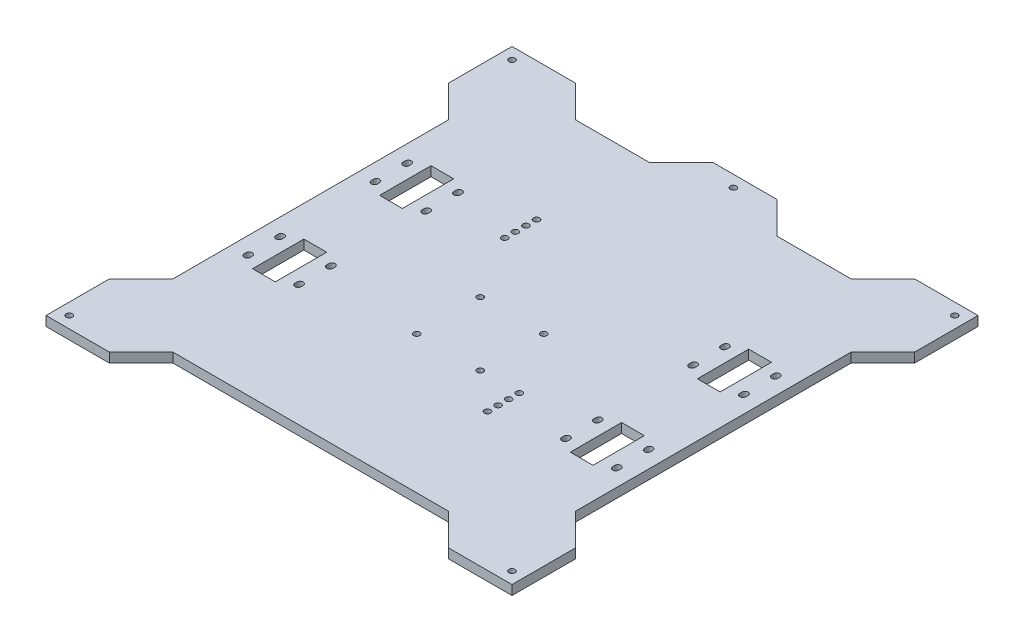
SolidWorks part; units mm, degrees
ref_plane "Front Plane" through (0, 0, 0) normal (0, 0, 1) x (1, 0, 0)
ref_plane "Top Plane" through (0, 0, 0) normal (0, 1, 0) x (1, 0, 0)
ref_plane "Right Plane" through (0, 0, 0) normal (1, 0, 0) x (0, 0, -1)
sketch "Sketch1" plane through (0, 0, 0) normal (0, 1, 0) x (1, 0, 0)
  line L1 (-110, 110) -> (110, 110)
  line L2 (-110, 110) -> (-110, -110)
  line L3 (-110, -110) -> (110, -110)
  line L4 (110, 110) -> (110, -110)
  line L5 (-110, 110) -> (110, -110) construction
  line L6 (-110, -110) -> (110, 110) construction
  point P0 (0, 0)
  dimension "D1" = 220
  dimension "D2" = 220
extrude "Square" add sketch "Sketch1" along normal blind 4.5
sketch "Sketch2" plane through (0, 4.5, 0) normal (0, 1, 0) x (1, 0, 0)
  line L0 (0, 110) -> (0, -110) construction
  line L1 (110, 110) -> (-110, 110) construction
  line L2 (-110, -110) -> (110, -110) construction
  line L3 (-110, 0) -> (110, 0) construction
  line L4 (-110, 110) -> (-110, -110) construction
  line L5 (110, -110) -> (110, 110) construction
  line L6 (75, 110) -> (75, -110) construction
  line L7 (75, 30) -> (0, 30) construction
  line L8 (75, -30) -> (0, -30) construction
  circle A0 centre (87, 38) radius 1.45
  circle A1 centre (87, 22) radius 1.45
  circle A2 centre (63, 22) radius 1.45
  circle A3 centre (63, 38) radius 1.45
  circle A4 centre (-63, 38) radius 1.45
  circle A5 centre (-63, 22) radius 1.45
  circle A6 centre (-87, 22) radius 1.45
  circle A7 centre (-87, 38) radius 1.45
  circle A8 centre (-87, 22) radius 1.45
  circle A9 centre (-87, 38) radius 1.45
  circle A10 centre (-63, 38) radius 1.45
  circle A11 centre (-63, 22) radius 1.45
  circle A12 centre (63, 22) radius 1.45
  circle A13 centre (63, 38) radius 1.45
  circle A14 centre (87, 38) radius 1.45
  circle A15 centre (87, 22) radius 1.45
  circle A16 centre (87, -22) radius 1.45
  circle A17 centre (87, -38) radius 1.45
  circle A18 centre (63, -38) radius 1.45
  circle A19 centre (63, -22) radius 1.45
  circle A20 centre (-63, -22) radius 1.45
  circle A21 centre (-63, -38) radius 1.45
  circle A22 centre (-87, -38) radius 1.45
  circle A23 centre (-87, -22) radius 1.45
  circle A24 centre (-87, -38) radius 1.45
  circle A25 centre (-87, -22) radius 1.45
  circle A26 centre (-63, -22) radius 1.45
  circle A27 centre (-63, -38) radius 1.45
  circle A28 centre (63, -38) radius 1.45
  circle A29 centre (63, -22) radius 1.45
  circle A30 centre (87, -22) radius 1.45
  circle A31 centre (87, -38) radius 1.45
  dimension "D6" = 2.9
  dimension "D7" = 2.9
  dimension "D1" = 75
  dimension "D2" = 30
  dimension "D3" = 16
  dimension "D5" = 12
extrude "LM8UU-Holders" cut sketch "Sketch2" against normal through all contours A7 | A6 | A5 | A4 | A20 | A21 | A22 | A23 | A19 | A18 | A17 | A16 | A1 | A0 | A3 | A2 region at (87, 4.5, -38) region at (87, 4.5, -22) region at (63, 4.5, -22) region at (63, 4.5, -38) region at (-63, 4.5, -38) region at (-63, 4.5, -22) region at (-87, 4.5, -22) region at (-87, 4.5, -38) region at (87, 4.5, 22) region at (87, 4.5, 38) region at (63, 4.5, 38) region at (63, 4.5, 22) region at (-63, 4.5, 22) region at (-63, 4.5, 38) region at (-87, 4.5, 38) region at (-87, 4.5, 22)
sketch "Sketch10" plane through (0, 4.5, 0) normal (0, 1, 0) x (1, 0, 0)
  line L0 (0, 110) -> (0, -79.9796) construction
  line L3 (-26.5242, 0) -> (110, 0) construction
  line L6 (75, 110) -> (75, -110) construction
  line L7 (75, 30) -> (-75, 30) construction
  line L8 (87, 22) -> (87, 23) construction
  line L9 (110, 110) -> (-110, 110) construction
  line L10 (110, -110) -> (110, 110) construction
  line L11 (85.55, 22) -> (85.55, 23)
  line L12 (88.45, 22) -> (88.45, 23)
  line L13 (87, 38) -> (87, 37) construction
  line L14 (88.45, 38) -> (88.45, 37)
  line L15 (85.55, 38) -> (85.55, 37)
  line L16 (63, 38) -> (63, 37) construction
  line L17 (61.55, 38) -> (61.55, 37)
  line L18 (64.45, 38) -> (64.45, 37)
  line L19 (63, 22) -> (63, 23) construction
  line L20 (64.45, 22) -> (64.45, 23)
  line L21 (61.55, 22) -> (61.55, 23)
  line L22 (75, -30) -> (-75, -30) construction
  line L23 (87, -22) -> (87, -23) construction
  line L24 (85.55, -22) -> (85.55, -23)
  line L25 (88.45, -22) -> (88.45, -23)
  line L26 (87, -38) -> (87, -37) construction
  line L27 (88.45, -38) -> (88.45, -37)
  line L28 (85.55, -38) -> (85.55, -37)
  line L29 (63, -38) -> (63, -37) construction
  line L30 (61.55, -38) -> (61.55, -37)
  line L31 (64.45, -38) -> (64.45, -37)
  line L32 (63, -22) -> (63, -23) construction
  line L33 (64.45, -22) -> (64.45, -23)
  line L34 (61.55, -22) -> (61.55, -23)
  line L35 (26.5242, 0) -> (-110, 0) construction
  line L36 (-87, 22) -> (-87, 23) construction
  line L37 (-85.55, 22) -> (-85.55, 23)
  line L38 (-88.45, 22) -> (-88.45, 23)
  line L39 (-87, 38) -> (-87, 37) construction
  line L40 (-88.45, 38) -> (-88.45, 37)
  line L41 (-85.55, 38) -> (-85.55, 37)
  line L42 (-63, 38) -> (-63, 37) construction
  line L43 (-61.55, 38) -> (-61.55, 37)
  line L44 (-64.45, 38) -> (-64.45, 37)
  line L45 (-63, 22) -> (-63, 23) construction
  line L46 (-64.45, 22) -> (-64.45, 23)
  line L47 (-61.55, 22) -> (-61.55, 23)
  line L48 (-87, -22) -> (-87, -23) construction
  line L49 (-85.55, -22) -> (-85.55, -23)
  line L50 (-88.45, -22) -> (-88.45, -23)
  line L51 (-87, -38) -> (-87, -37) construction
  line L52 (-88.45, -38) -> (-88.45, -37)
  line L53 (-85.55, -38) -> (-85.55, -37)
  line L54 (-63, -38) -> (-63, -37) construction
  line L55 (-61.55, -38) -> (-61.55, -37)
  line L56 (-64.45, -38) -> (-64.45, -37)
  line L57 (-63, -22) -> (-63, -23) construction
  line L58 (-64.45, -22) -> (-64.45, -23)
  line L59 (-61.55, -22) -> (-61.55, -23)
  arc A0 (61.55, 38) -> (64.45, 38) centre (63, 38) cw
  arc A1 (88.45, 38) -> (85.55, 38) centre (87, 38) ccw
  arc A2 (85.55, 22) -> (88.45, 22) centre (87, 22) ccw
  arc A3 (88.45, 23) -> (85.55, 23) centre (87, 23) ccw
  arc A4 (85.55, 37) -> (88.45, 37) centre (87, 37) ccw
  arc A5 (64.45, 37) -> (61.55, 37) centre (63, 37) cw
  arc A6 (64.45, 22) -> (61.55, 22) centre (63, 22) cw
  arc A7 (61.55, 23) -> (64.45, 23) centre (63, 23) cw
  arc A8 (85.55, -22) -> (88.45, -22) centre (87, -22) cw
  arc A9 (88.45, -23) -> (85.55, -23) centre (87, -23) cw
  arc A10 (88.45, -38) -> (85.55, -38) centre (87, -38) cw
  arc A11 (85.55, -37) -> (88.45, -37) centre (87, -37) cw
  arc A12 (61.55, -38) -> (64.45, -38) centre (63, -38) ccw
  arc A13 (64.45, -37) -> (61.55, -37) centre (63, -37) ccw
  arc A14 (64.45, -22) -> (61.55, -22) centre (63, -22) ccw
  arc A15 (61.55, -23) -> (64.45, -23) centre (63, -23) ccw
  arc A16 (-85.55, 22) -> (-88.45, 22) centre (-87, 22) cw
  arc A17 (-88.45, 23) -> (-85.55, 23) centre (-87, 23) cw
  arc A18 (-88.45, 38) -> (-85.55, 38) centre (-87, 38) cw
  arc A19 (-85.55, 37) -> (-88.45, 37) centre (-87, 37) cw
  arc A20 (-61.55, 38) -> (-64.45, 38) centre (-63, 38) ccw
  arc A21 (-64.45, 37) -> (-61.55, 37) centre (-63, 37) ccw
  arc A22 (-64.45, 22) -> (-61.55, 22) centre (-63, 22) ccw
  arc A23 (-61.55, 23) -> (-64.45, 23) centre (-63, 23) ccw
  arc A24 (-85.55, -22) -> (-88.45, -22) centre (-87, -22) ccw
  arc A25 (-88.45, -23) -> (-85.55, -23) centre (-87, -23) ccw
  arc A26 (-88.45, -38) -> (-85.55, -38) centre (-87, -38) ccw
  arc A27 (-85.55, -37) -> (-88.45, -37) centre (-87, -37) ccw
  arc A28 (-61.55, -38) -> (-64.45, -38) centre (-63, -38) cw
  arc A29 (-64.45, -37) -> (-61.55, -37) centre (-63, -37) cw
  arc A30 (-64.45, -22) -> (-61.55, -22) centre (-63, -22) cw
  arc A31 (-61.55, -23) -> (-64.45, -23) centre (-63, -23) cw
  point P8 (87, 22.5)
  point P19 (87, 37.5)
  point P28 (63, 37.5)
  point P35 (63, 22.5)
  point P44 (87, -22.5)
  point P51 (87, -37.5)
  point P58 (63, -37.5)
  point P65 (63, -22.5)
  point P73 (0, 30)
  point P74 (0, -30)
  point P76 (-87, 22.5)
  point P83 (-87, 37.5)
  point P90 (-63, 37.5)
  point P97 (-63, 22.5)
  point P104 (-87, -22.5)
  point P111 (-87, -37.5)
  point P118 (-63, -37.5)
  point P125 (-63, -22.5)
  dimension "D1" = 75
  dimension "D2" = 30
  dimension "D3" = 16
  dimension "D5" = 12
  dimension "D4" = 1.45
  dimension "D7" = 1.45
  dimension "D8" = 1
  dimension "D9" = 1
sketch "Sketch3" plane through (0, 4.5, 0) normal (0, 1, 0) x (1, 0, 0)
  line L0 (0, -110) -> (0, 110) construction
  line L1 (-110, -110) -> (110, -110) construction
  line L2 (110, 110) -> (-110, 110) construction
  line L3 (110, -15) -> (-110, -15) construction
  line L6 (15, -30) -> (-15, -30) construction
  line L7 (15, 0) -> (-15, 0) construction
  line L8 (110, -110) -> (110, 110) construction
  line L9 (-110, 110) -> (-110, -110) construction
  line L10 (110, 0) -> (-110, 0) construction
  circle A0 centre (-15, -30) radius 1.45
  circle A1 centre (15, -30) radius 1.45
  circle A2 centre (15, 0) radius 1.45
  circle A3 centre (-15, 0) radius 1.45
  point P16 (0, -30)
  dimension "D1" = 2.9
  dimension "D2" = 15
  dimension "D3" = 15
  dimension "D5" = 15
extrude "DefaultBelt" cut sketch "Sketch3" against normal through all
sketch "Sketch4" plane through (0, 4.5, 0) normal (0, 1, 0) x (1, 0, 0)
  line L0 (0, 110) -> (0, -110) construction
  line L1 (110, 110) -> (-110, 110) construction
  line L2 (-110, -110) -> (110, -110) construction
  line L3 (-15, -1.45) -> (-15, -28.55) construction
  line L4 (15, -28.55) -> (15, -1.45) construction
  line L5 (15, -15) -> (-15, -15) construction
  arc A0 (-0.7348, 6.25) -> (0.7348, 6.25) centre (0, 5) ccw
  arc A1 (0.7348, 6.25) -> (-0.7348, 6.25) centre (0, 7.5) ccw
  arc A2 (0.7348, -36.25) -> (-0.7348, -36.25) centre (0, -37.5) cw
  arc A3 (-0.7348, -36.25) -> (0.7348, -36.25) centre (0, -35) cw
  circle A4 centre (-15, 0) radius 1.45 construction
  circle A5 centre (-15, -30) radius 1.45 construction
  circle A6 centre (15, -30) radius 1.45 construction
  circle A7 centre (15, 0) radius 1.45 construction
  dimension "D1" = 2.9
  dimension "D2" = 2.9
  dimension "D3" = 20
  dimension "D4" = 22.5
extrude "BeltOptions" [suppressed] cut sketch "Sketch4" against normal through all
sketch "Sketch5" plane through (0, 4.5, 0) normal (0, 1, 0) x (1, 0, 0)
  line L0 (-110, 0) -> (110, 0) construction
  line L1 (-110, 110) -> (-110, -110) construction
  line L2 (110, -110) -> (110, 110) construction
  line L3 (0, 110) -> (0, -110) construction
  line L4 (110, 110) -> (-110, 110) construction
  line L5 (-110, 110) -> (-110, 80)
  line L6 (-110, 80) -> (-95, 65)
  line L7 (-95, 65) -> (-95, -65)
  line L8 (0, 0) -> (-110, 110) construction
  line L9 (-65, 95) -> (65, 95)
  line L10 (-80, 110) -> (-65, 95)
  line L11 (-110, 110) -> (-80, 110)
  line L12 (-95, 65) -> (-95, -65)
  line L13 (0, 0) -> (110, 110) construction
  line L14 (95, 65) -> (95, -65)
  line L15 (110, 110) -> (80, 110)
  line L16 (80, 110) -> (65, 95)
  line L17 (95, 65) -> (95, -65)
  line L18 (110, 80) -> (95, 65)
  line L19 (110, 110) -> (110, 80)
  line L20 (0, 0) -> (110, -110) construction
  line L21 (0, 0) -> (-110, -110) construction
  line L22 (110, -110) -> (110, -80)
  line L23 (110, -80) -> (95, -65)
  line L24 (80, -110) -> (65, -95)
  line L25 (110, -110) -> (80, -110)
  line L26 (-110, -110) -> (-80, -110)
  line L27 (-80, -110) -> (-65, -95)
  line L28 (-65, -95) -> (65, -95)
  line L29 (-110, -80) -> (-95, -65)
  line L30 (-110, -110) -> (-110, -80)
  point P24 (0, 95)
  point P32 (95, 0)
  point P35 (-95, 0)
  point P36 (0, -95)
  circle M16 centre (15, -30) radius 1.45
  circle M18 centre (63, 38) radius 1.45
  circle M20 centre (87, 22) radius 1.45
  circle M22 centre (87, -38) radius 1.45
  circle M23 centre (63, -38) radius 1.45
  circle M24 centre (63, -22) radius 1.45
  circle M25 centre (-87, -22) radius 1.45
  circle M26 centre (-87, -38) radius 1.45
  circle M27 centre (-63, -38) radius 1.45
  circle M28 centre (-63, -22) radius 1.45
  circle M29 centre (-63, 38) radius 1.45
  circle M30 centre (-63, 22) radius 1.45
  circle M31 centre (-87, 22) radius 1.45
  circle M32 centre (-87, 38) radius 1.45
  line M33 (110, -110) -> (110, 110)
  line M34 (110, 110) -> (-110, 110)
  line M35 (-110, 110) -> (-110, -110)
  line M36 (-110, -110) -> (110, -110)
  dimension "D1" = 15
  dimension "D2" = 30
  dimension "D3" = 45
  dimension "D4" = 45
extrude "Shaping" cut sketch "Sketch5" against normal blind 10 flip side to cut contours L29 L27 L28 L24 L23 L14 L18 L16 L9 L10 L6 L7 M35 M36 M33 M34 M16 M18 M20 M22 M24 M26 M28 M30 M32 M31 M29 M27 M25 M23 region at (0.037, 4.5, -0.0113)
sketch "Sketch6" plane through (0, 4.5, 0) normal (0, 1, 0) x (1, 0, 0)
  line L0 (-110, 110) -> (110, -110) construction
  line L1 (-110, -110) -> (110, 110) construction
  line L2 (110, 80) -> (110, 110) construction
  line L3 (0, 95) -> (0, -95) construction
  line L4 (-65, 95) -> (65, 95) construction
  line L5 (-65, -95) -> (65, -95) construction
  line L6 (-95, 0) -> (95, 0) construction
  line L7 (-95, 65) -> (-95, -65) construction
  line L8 (95, 65) -> (95, -65) construction
  circle A0 centre (-104.5, 104.5) radius 1.45
  circle A1 centre (104.5, 104.5) radius 1.45
  circle A2 centre (104.5, -104.5) radius 1.45
  circle A3 centre (-104.5, -104.5) radius 1.45
  dimension "D2" = 2.9
  dimension "D1" = 45
  dimension "D3" = 104.5
extrude "Cut-Extrude5" cut sketch "Sketch6" against normal through all
sketch "Sketch7" plane through (0, 4.5, 0) normal (0, 1, 0) x (1, 0, 0)
  line L0 (-87, 38) -> (-63, 22) construction
  line L1 (-63, 22) -> (-87, 22) construction
  line L2 (-87, 22) -> (-63, 38) construction
  line L3 (-63, 38) -> (-87, 38) construction
  line L4 (-95, 0) -> (95, 0) construction
  line L5 (-80.375, 42.125) -> (-69.625, 42.125)
  line L6 (-80.375, 42.125) -> (-80.375, 17.875)
  line L7 (-80.375, 17.875) -> (-69.625, 17.875)
  line L8 (-69.625, 42.125) -> (-69.625, 17.875)
  line L9 (-80.375, 42.125) -> (-69.625, 17.875) construction
  line L10 (-80.375, 17.875) -> (-69.625, 42.125) construction
  line L11 (-95, 65) -> (-95, -65) construction
  line L12 (95, 65) -> (95, -65) construction
  line L13 (0, -95) -> (0, 95) construction
  line L14 (-65, -95) -> (65, -95) construction
  line L15 (-65, 95) -> (65, 95) construction
  line L16 (-80.375, -17.875) -> (-69.625, -42.125) construction
  line L17 (-80.375, -42.125) -> (-69.625, -17.875) construction
  line L18 (-63, -38) -> (-87, -38) construction
  line L19 (-87, -22) -> (-63, -38) construction
  line L20 (-63, -22) -> (-87, -22) construction
  line L21 (-87, -38) -> (-63, -22) construction
  line L22 (-69.625, -42.125) -> (-69.625, -17.875)
  line L23 (-80.375, -17.875) -> (-69.625, -17.875)
  line L24 (-80.375, -42.125) -> (-80.375, -17.875)
  line L25 (-80.375, -42.125) -> (-69.625, -42.125)
  line L26 (-80.375, 17.875) -> (-69.625, 42.125) construction
  line L27 (80.375, 17.875) -> (69.625, 42.125) construction
  line L28 (87, -38) -> (63, -22) construction
  line L29 (63, -22) -> (87, -22) construction
  line L30 (87, -22) -> (63, -38) construction
  line L31 (63, -38) -> (87, -38) construction
  line L32 (80.375, -42.125) -> (69.625, -17.875) construction
  line L33 (80.375, -17.875) -> (69.625, -42.125) construction
  line L34 (80.375, 17.875) -> (69.625, 42.125) construction
  line L35 (80.375, 42.125) -> (69.625, 17.875) construction
  line L36 (63, 38) -> (87, 38) construction
  line L37 (87, 22) -> (63, 38) construction
  line L38 (63, 22) -> (87, 22) construction
  line L39 (87, 38) -> (63, 22) construction
  line L40 (80.375, -42.125) -> (69.625, -42.125)
  line L41 (80.375, -42.125) -> (80.375, -17.875)
  line L42 (80.375, -17.875) -> (69.625, -17.875)
  line L43 (69.625, -42.125) -> (69.625, -17.875)
  line L44 (69.625, 42.125) -> (69.625, 17.875)
  line L45 (80.375, 17.875) -> (69.625, 17.875)
  line L46 (80.375, 42.125) -> (80.375, 17.875)
  line L47 (80.375, 42.125) -> (69.625, 42.125)
  point P4 (-75, 30)
  point P33 (-75, -30)
  point P50 (75, -30)
  point P51 (75, 30)
  dimension "D1" = 10.75
  dimension "D2" = 24.25
extrude "Cut-Extrude6" cut sketch "Sketch7" against normal through all
sketch "Sketch8" plane through (0, 4.5, 0) normal (0, 1, 0) x (1, 0, 0)
  line L0 (0, 0) -> (0, 95) construction
  line L1 (0, 0) -> (-66.8115, 0) construction
  line L3 (-65, 95) -> (65, 95) construction
  line L4 (-33.45, 45) -> (-33.45, 30) construction
  line L5 (-33.45, 45) -> (-33.45, 30) construction
  line L6 (33.45, -45) -> (33.45, -30) construction
  circle A0 centre (-33.45, 45) radius 1.45
  circle A1 centre (-33.45, 40) radius 1.45
  circle A2 centre (-33.45, 35) radius 1.45
  circle A3 centre (-33.45, 30) radius 1.45
  circle A8 centre (33.45, -45) radius 1.45
  circle A9 centre (33.45, -40) radius 1.45
  circle A10 centre (33.45, -35) radius 1.45
  circle A11 centre (33.45, -30) radius 1.45
  dimension "D1" = 2.9
  dimension "D2" = 50
  dimension "D4" = 33.45
extrude "EndstopTrigger" cut sketch "Sketch8" against normal through all
pattern_linear "LPattern1" [suppressed] count 2 spacing 30 of bodies 108
sketch "Sketch9" plane through (0, 4.5, 0) normal (0, 1, 0) x (1, 0, 0)
  line L0 (-80, 110) -> (-110, 110) construction
  line L1 (-65, 95) -> (65, 95) construction
  line L7 (-95, 0) -> (95, 0) construction
  line L8 (-95, 65) -> (-95, -65) construction
  line L11 (95, 65) -> (95, -65) construction
  line L12 (-104.5, 104.5) -> (104.5, 104.5) construction
  line L13 (0, 110) -> (0, 95) construction
  line L14 (-80, 110) -> (80, 110) construction
  line L15 (15, 110) -> (30, 95)
  line L16 (-30, 95) -> (30, 95)
  line L17 (-15, 110) -> (-30, 95)
  line L18 (15, 110) -> (-15, 110)
  circle A1 centre (0, 104.5) radius 1.45
  dimension "D2" = 30
  dimension "D3" = 2.9
  dimension "D1" = 45
  dimension "D4" = 45
extrude "Boss-Extrude1" add sketch "Sketch9" against normal through all
extrude "HolesToSlots" cut sketch "Sketch10" against normal through all
sketch "Sketch11" plane through (0, 4.5, 0) normal (0, 1, 0) x (1, 0, 0)
  line L0 (0, -95) -> (0, 0) construction
  line L1 (-65, -95) -> (65, -95) construction
  line L2 (95, 0) -> (0, 0) construction
  line L3 (95, 65) -> (95, -65) construction
  line L4 (0, 0) -> (110, -110) construction
  line L5 (-69.1421, -85) -> (-5, -85)
  line L6 (-69.1421, -85) -> (-84.1421, -100)
  line L7 (-84.1421, -100) -> (-100, -100)
  line L8 (-100, -100) -> (-100, -84.1421)
  line L9 (-100, -84.1421) -> (-85, -69.1421)
  line L10 (-85, -69.1421) -> (-85, -52.125)
  line L11 (-85, -52.125) -> (-5, -52.125)
  line L12 (-80, -110) -> (-65, -95) construction
  line L13 (-110, -80) -> (-95, -65) construction
  line L14 (-110, -80) -> (-110, -110) construction
  line L15 (-110, -110) -> (-80, -110) construction
  line L16 (-80.375, -42.125) -> (-69.625, -42.125) construction
  line L17 (-95, 65) -> (-95, -65) construction
  line L18 (-5, -52.125) -> (-5, -85)
  line L19 (5, -52.125) -> (5, -85)
  line L20 (85, -52.125) -> (5, -52.125)
  line L21 (85, -69.1421) -> (85, -52.125)
  line L22 (100, -84.1421) -> (85, -69.1421)
  line L23 (100, -100) -> (100, -84.1421)
  line L24 (84.1421, -100) -> (100, -100)
  line L25 (69.1421, -85) -> (84.1421, -100)
  line L26 (69.1421, -85) -> (5, -85)
  line L27 (69.1421, 85) -> (5, 85)
  line L28 (69.1421, 85) -> (84.1421, 100)
  line L29 (84.1421, 100) -> (100, 100)
  line L30 (100, 100) -> (100, 84.1421)
  line L31 (100, 84.1421) -> (85, 69.1421)
  line L32 (85, 69.1421) -> (85, 52.125)
  line L33 (85, 52.125) -> (5, 52.125)
  line L34 (5, 52.125) -> (5, 85)
  line L35 (-5, 52.125) -> (-5, 85)
  line L36 (-85, 52.125) -> (-5, 52.125)
  line L37 (-85, 69.1421) -> (-85, 52.125)
  line L38 (-100, 84.1421) -> (-85, 69.1421)
  line L39 (-100, 100) -> (-100, 84.1421)
  line L40 (-84.1421, 100) -> (-100, 100)
  line L41 (-69.1421, 85) -> (-84.1421, 100)
  line L42 (-69.1421, 85) -> (-5, 85)
  dimension "D1" = 10
  dimension "D2" = 10
  dimension "D3" = 10
  dimension "D4" = 10
  dimension "D5" = 10
  dimension "D6" = 10
  dimension "D7" = 10
  dimension "D8" = 5
extrude "Cut-Extrude7" [suppressed] cut sketch "Sketch11" against normal through all
sketch "Sketch12" [suppressed] plane through (0, 4.5, 0) normal (0, 1, 0) x (1, 0, 0)
  line L0 (0, 0) -> (-110, -110) construction
  line L1 (-110, -110) -> (-80, -110) construction
  line L2 (-110, -80) -> (80, 110) construction
  line L3 (110, 80) -> (-80, -110) construction
  line L4 (-95, -65) -> (-65, -95) construction
  line L5 (0, 0) -> (0, -95) construction
  line L6 (-65, -95) -> (65, -95) construction
  line L7 (95, 0) -> (-95, 0) construction
  line L8 (-95, 65) -> (-95, -65) construction
  line L9 (-100, -100) -> (-100, -84.1421)
  line L10 (-100, -84.1421) -> (-59.2893, -43.4315)
  line L11 (-59.2893, -43.4315) -> (-43.4315, -43.4315)
  line L12 (-110, -80) -> (-110, -110) construction
  line L13 (-100, -100) -> (-84.1421, -100)
  line L14 (-84.1421, -100) -> (-43.4315, -59.2893)
  line L15 (-43.4315, -59.2893) -> (-43.4315, -43.4315)
  line L16 (55, -85) -> (-55, -85)
  line L17 (-55, -85) -> (-29.2893, -59.2893)
  line L18 (-29.2893, -59.2893) -> (29.2893, -59.2893)
  line L19 (95, -65) -> (65, -95) construction
  line L20 (0, 0) -> (110, -110) construction
  line L21 (55, -85) -> (29.2893, -59.2893)
  line L22 (43.4315, -59.2893) -> (43.4315, -43.4315)
  line L23 (84.1421, -100) -> (43.4315, -59.2893)
  line L24 (100, -100) -> (84.1421, -100)
  line L25 (59.2893, -43.4315) -> (43.4315, -43.4315)
  line L26 (100, -84.1421) -> (59.2893, -43.4315)
  line L27 (100, -100) -> (100, -84.1421)
  line L28 (95, 65) -> (65, 95) construction
  line L29 (-95, 65) -> (-65, 95) construction
  line L30 (100, 100) -> (100, 84.1421)
  line L31 (100, 84.1421) -> (59.2893, 43.4315)
  line L32 (59.2893, 43.4315) -> (43.4315, 43.4315)
  line L33 (100, 100) -> (84.1421, 100)
  line L34 (84.1421, 100) -> (43.4315, 59.2893)
  line L35 (43.4315, 59.2893) -> (43.4315, 43.4315)
  line L36 (55, 85) -> (29.2893, 59.2893)
  line L37 (-29.2893, 59.2893) -> (29.2893, 59.2893)
  line L38 (-55, 85) -> (-29.2893, 59.2893)
  line L39 (55, 85) -> (-55, 85)
  line L40 (-43.4315, 59.2893) -> (-43.4315, 43.4315)
  line L41 (-84.1421, 100) -> (-43.4315, 59.2893)
  line L42 (-100, 100) -> (-84.1421, 100)
  line L43 (-59.2893, 43.4315) -> (-43.4315, 43.4315)
  line L44 (-100, 84.1421) -> (-59.2893, 43.4315)
  line L45 (-100, 100) -> (-100, 84.1421)
  point P40 (0, -59.2893)
  point P41 (0, -85)
  point P67 (0, 85)
  point P68 (0, 59.2893)
  dimension "D1" = 10
  dimension "D2" = 10
  dimension "D3" = 80
  dimension "D4" = 10
  dimension "D5" = 10
  dimension "D6" = 0
extrude "Cut-Extrude8" [suppressed] cut sketch "Sketch12" against normal through all
sketch "Sketch14" [suppressed] plane through (0, 4.5, 0) normal (0, 1, 0) x (1, 0, 0)
  line L0 (0, 85) -> (0, 110) construction
  line L1 (55, 85) -> (-55, 85) construction
  line L2 (15, 110) -> (-15, 110) construction
  line L3 (10.8579, 100) -> (-10.8579, 100)
  line L4 (-10.8579, 100) -> (-25.8579, 85)
  line L5 (-25.8579, 85) -> (25.8579, 85)
  line L6 (-15, 110) -> (-30, 95) construction
  line L7 (10.8579, 100) -> (25.8579, 85)
  point P13 (0, 100)
  dimension "D1" = 10
  dimension "D2" = 10
extrude "Cut-Extrude10" [suppressed] cut sketch "Sketch14" against normal through all
sketch "Sketch13" [suppressed] plane through (0, 4.5, 0) normal (0, 1, 0) x (1, 0, 0)
  line L0 (-59.2893, 43.4315) -> (-59.2893, -43.4315) construction
  line L1 (-100, 84.1421) -> (-59.2893, 43.4315) construction
  line L2 (-59.2893, 0) -> (0, 0) construction
  line L3 (-59.2893, 33.4315) -> (-59.2893, -33.4315)
  line L4 (-59.2893, -33.4315) -> (-43.4315, -33.4315)
  line L5 (-43.4315, -33.4315) -> (-43.4315, 33.4315)
  line L6 (-43.4315, 33.4315) -> (-59.2893, 33.4315)
  line L7 (-59.2893, 43.4315) -> (-43.4315, 43.4315) construction
  line L8 (-43.4315, -43.4315) -> (-59.2893, -43.4315) construction
  line L9 (-43.4315, 43.4315) -> (-43.4315, 59.2893) construction
  line L10 (0, 0) -> (0, 43.4315) construction
  line L11 (59.2893, 43.4315) -> (59.2893, -43.4315) construction
  line L12 (43.4315, 33.4315) -> (59.2893, 33.4315)
  line L13 (43.4315, -33.4315) -> (43.4315, 33.4315)
  line L14 (59.2893, -33.4315) -> (43.4315, -33.4315)
  line L15 (59.2893, 33.4315) -> (59.2893, -33.4315)
  line L16 (110, -110) -> (0, 0) construction
  line L17 (55, -85) -> (29.2893, -59.2893) construction
  line L18 (-33.4315, -43.2893) -> (33.4315, -43.2893)
  line L19 (-33.4315, -43.2893) -> (-33.4315, -63.4315)
  line L20 (-33.4315, -63.4315) -> (33.4315, -63.4315)
  line L21 (33.4315, -43.2893) -> (33.4315, -63.4315)
  line L22 (-33.4315, -43.2893) -> (33.4315, -63.4315) construction
  line L23 (-33.4315, -63.4315) -> (33.4315, -43.2893) construction
  line L24 (-43.4315, -59.2893) -> (-43.4315, -43.4315) construction
  line L25 (0, -53.3604) -> (0, -63.4315) construction
  line L26 (55, 85) -> (25.8579, 85) construction
  line L28 (43.4315, -43.4315) -> (43.4315, -59.2893) construction
  line L29 (29.2893, -59.2893) -> (-29.2893, -59.2893) construction
  line L30 (43.4315, 59.2893) -> (43.4315, 43.4315) construction
  line L31 (-33.4315, 83) -> (33.4315, 83)
  line L32 (-33.4315, 83) -> (-33.4315, 15)
  line L33 (-33.4315, 15) -> (33.4315, 15)
  line L34 (33.4315, 83) -> (33.4315, 15)
  line L35 (-33.4315, 83) -> (33.4315, 15) construction
  line L36 (-33.4315, 15) -> (33.4315, 83) construction
  point P27 (0, -53.3604)
  point P43 (0, 49)
  dimension "D1" = 10
  dimension "D2" = 10
  dimension "D3" = 10
  dimension "D4" = 10
  dimension "D5" = 16
  dimension "D6" = 10
  dimension "D7" = 10
  dimension "D8" = 15
  dimension "D9" = 2
extrude "Cut-Extrude9" [suppressed] cut sketch "Sketch13" against normal through all
sketch "Sketch15" [suppressed] plane through (0, 4.5, 0) normal (0, 1, 0) x (1, 0, 0)
  line L0 (-59.2893, 0) -> (-95, 0) construction
  line L1 (-59.2893, 33.4315) -> (-59.2893, -33.4315) construction
  line L2 (-95, 65) -> (-95, -65) construction
  line L3 (-80.5, 17.875) -> (-69.5, 17.875) construction
  line L4 (-59.2893, -15) -> (-59.2893, -7.875)
  line L5 (-85, -7.875) -> (-85, 7.875)
  line L6 (-85, 7.875) -> (-66.4143, 7.875)
  line L7 (-59.2893, -7.875) -> (-59.2893, 7.875)
  line L8 (-66.4143, -7.875) -> (-59.2893, -15)
  line L9 (-85, -7.875) -> (-66.4143, -7.875)
  line L11 (-66.4143, 7.875) -> (-59.2893, 15)
  line L12 (-59.2893, 15) -> (-59.2893, 7.875)
  line L13 (0, 0) -> (0, -21.7485) construction
  line L14 (59.2893, 0) -> (95, 0) construction
  line L15 (59.2893, 15) -> (59.2893, 7.875)
  line L16 (66.4143, 7.875) -> (59.2893, 15)
  line L17 (85, -7.875) -> (66.4143, -7.875)
  line L18 (66.4143, -7.875) -> (59.2893, -15)
  line L19 (59.2893, -7.875) -> (59.2893, 7.875)
  line L20 (85, 7.875) -> (66.4143, 7.875)
  line L21 (85, -7.875) -> (85, 7.875)
  line L22 (59.2893, -15) -> (59.2893, -7.875)
  line L23 (-59.2893, 0) -> (-95, 0) construction
  point P17 (-85, 0)
  point P30 (85, 0)
  dimension "D1" = 10
  dimension "D2" = 10
  dimension "D4" = 45
  dimension "D5" = 15
extrude "Cut-Extrude11" [suppressed] cut sketch "Sketch15" against normal through all
sketch "Sketch16" [suppressed] plane through (0, 4.5, 0) normal (0, 1, 0) x (1, 0, 0)
  line L0 (-85, -69.1421) -> (-85, -52.125)
  line L1 (-59.2893, -43.4315) -> (-100, -84.1421) construction
  line L2 (-85, -52.125) -> (-67.9829, -52.125)
  line L3 (-67.9829, -52.125) -> (-85, -69.1421)
  line L4 (-95, 65) -> (-95, -65) construction
  line L5 (-80.5, -42.125) -> (-69.5, -42.125) construction
  line L6 (-95, 0) -> (95, 0) construction
  line L7 (95, 65) -> (95, -65) construction
  line L8 (0, 0) -> (0, -95) construction
  line L9 (-65, -95) -> (65, -95) construction
  line L10 (-67.9829, 52.125) -> (-85, 69.1421)
  line L11 (-85, 52.125) -> (-67.9829, 52.125)
  line L12 (-85, 69.1421) -> (-85, 52.125)
  line L13 (-67.9829, -52.125) -> (-85, -69.1421)
  line L14 (67.9829, -52.125) -> (85, -69.1421)
  line L15 (85, 69.1421) -> (85, 52.125)
  line L16 (85, 52.125) -> (67.9829, 52.125)
  line L17 (67.9829, 52.125) -> (85, 69.1421)
  line L18 (67.9829, -52.125) -> (85, -69.1421)
  line L19 (85, -52.125) -> (67.9829, -52.125)
  line L20 (85, -69.1421) -> (85, -52.125)
  line L21 (100, -84.1421) -> (59.2893, -43.4315) construction
  line L23 (69.5, -42.125) -> (80.5, -42.125) construction
  line L24 (80.5, 42.125) -> (69.5, 42.125) construction
  line L25 (59.2893, 43.4315) -> (100, 84.1421) construction
  line L26 (-100, 84.1421) -> (-59.2893, 43.4315) construction
  line L27 (-69.5, 42.125) -> (-80.5, 42.125) construction
  dimension "D1" = 10
  dimension "D2" = 10
  dimension "D3" = 10
  dimension "D4" = 10
  dimension "D5" = 10
  dimension "D6" = 10
  dimension "D7" = 10
  dimension "D8" = 10
extrude "Cut-Extrude12" [suppressed] cut sketch "Sketch16" against normal through all contours L3 L2 L0 | L10 L12 L11 | L17 L16 L15 | L14 L20 L19
equation "\"X-ROD-SPACING\"=45"
equation "\"Y-ROD-SPACING\"=75"
equation "\"Z-ROD-SPACING\"=17.5"
equation "\"Y-BED-OFFSET\"=2"
equation "\"Y-BED-ROD-INSET\"=3.5"
equation "\"T-SLOT-NUT-FILLET-RADIUS\"=0.5"
equation "\"T-SLOT-SCREW-SHAFT-RADIUS\"=1.55"
equation "\"T-SLOT-SCREW-SHAFT-CUTOUT-LENGTH\"=11"
equation "\"T-SLOT-NUT-DEPTH\"=3.5"
equation "\"T-SLOT-NUT-WIDTH\"=2.85"
equation "\"T-SLOT-NUT-END-DISTANCE\"=8"
equation "\"ACRYLIC-THICKNESS\"=10"
equation "\"ACRYLIC-THICKNESS2\"=4.5"
equation "\"ACRYLIC-TAB-CUTOUT-SIZE\"=\"ACRYLIC-THICKNESS\"+\"ACRYLIC-TAB-TOLERANCE\"*2"
equation "\"ACRYLIC-TAB-WIDTH\"=\"ACRYLIC-THICKNESS\""
equation "\"ACRYLIC-M3-HOLE\"=2.9"
equation "\"SMOOTHROD-CAP-SCREW-DISTANCE\"=20"
equation "\"FRAME-WIDTH-INNER\"=370"
equation "\"NEMA17-HOLE-SPACING\"=31"
equation "\"NEMA17-CENTRAL-CUTOUT\"=22.5"
equation "\"Z-BRACKET-REACH\"=55"
equation "\"TOP-BRACKET-SPACING\"=40"
equation "\"SMOOTHROD-X-LENGTH\"=350"
equation "\"SMOOTHROD-Y-LENGTH\"=350"
equation "\"SMOOTHROD-Z-LENGTH\"=350"
equation "\"SMOOTHROD-TIGHTENING-HEADROOM\"=.25"
equation "\"LEADSCREW-Z-LENGTH\"=300"
equation "\"SCREW-LENGTH-FRAME\"=\"ACRYLIC-THICKNESS\" + 10"
equation "\"SCREW-HEAD-RADIUS\"=6"
equation "\"PRINTED-X-SMOOTHROD-DIAMETER\"=9.0"
equation "\"PRINTED-X-SMOOTHROD-CUTOUT\"=10"
equation "\"PRINTED-X-BASE-HEIGHT\"=10"
equation "\"PRINTED-LM8UU-CUTOUT-SIZE\"=15.5"
equation "\"PRINTED-LM8UU-CUTOUT-LENGTH\"=24.5"
equation "\"PRINTED-X-IDLER-HEIGHT\"=16"
equation "\"PSU-MOUNTING-WIDTH\"=95"
equation "\"PSU-MOUNTING-HEIGHT\"=177"
equation "\"Y-BELT-TO-ROD-DISTANCE\"=20"
equation "\"D6@Sketch2\"=\"ACRYLIC-M3-HOLE\""
equation "\"D7@Sketch2\"=\"ACRYLIC-M3-HOLE\""
equation "\"D1@Sketch2\"=\"Y-ROD-SPACING\""
equation "\"D1@Sketch3\"=\"ACRYLIC-M3-HOLE\""
equation "\"D2@Sketch6\"=\"ACRYLIC-M3-HOLE\""
equation "\"Y-BED-SCREW-SPACING\"=209"
equation "\"Y-BED-SCREW-CUTOUT-SLOT-HEIGHT\"=2"
equation "\"ACRYLIC-TAB-TOLERANCE\"=-.05"
equation "\"Z-ROD-INSET\"=13.5"
equation "\"SCREW-LENGTH-MOTOR\"=\"ACRYLIC-THICKNESS\" + 5"
equation "\"SCREW-LENGTH-EXTRUDER\"=28"
equation "\"PRINTED-M3-HOLE\"=3.5"
equation "\"SPOOL-HOLDER-ROD-SPACING\"=150"
equation "\"ACRYLIC-X-CARRIAGE-WIDTH\"=55"
equation "\"ACRYLIC-X-CARRIAGE-HEIGHT\"=75"
equation "\"ACRYLIC-X-CARRIAGE-LM8UU-CUTOUT-WIDTH\"=24.25"
equation "\"ACRYLIC-X-CARRIAGE-LM8UU-CUTOUT-HEIGHT\"=11.0"
equation "\"ACRYLIC-X-CARRIAGE-SCREW-SPACING-X\"=15"
equation "\"ACRYLIC-X-CARRIAGE-SCREW-SPACING-Y\"=33"
equation "\"ACRYLIC-X-CARRIAGE-CENTER-TAB-SPACING\"=14"
equation "\"ACRYLIC-X-CARRIAGE-EXTRUDER-OFFSET\"=26"
equation "\"ACRYLIC-X-CARRIAGE-EXTRUDER-ANGLE\"=90"
equation "\"ACRYLIC-X-CARRIAGE-EXTRUDER-SHELF-DEPTH\"=\"ACRYLIC-X-CARRIAGE-EXTRUDER-OFFSET\" + 28"
equation "\"ACRYLIC-X-CARRIAGE-EXTRUDER-BRACE-SPACING\"=23"
equation "\"ACRYLIC-X-CARRIAGE-EXTRUDER-BRACE-TAB-OFFSET\"=20"
equation "\"ACRYLIC-X-CARRIAGE-EXTRUDER-BRACE-HEIGHT\"=35"
equation "\"ACRYLIC-X-CARRIAGE-EXTRUDER-BRACE-SCREW-SPACING\"=22"
equation "\"ACRYLIC-X-CARRIAGE-DUAL-WIDTH-MULTIPLIER\"=1.65"
equation "\"ACRYLIC-X-CARRIAGE-DUAL-HOTEND-SPACING\"=42"
equation "\"ACRYLIC-X-CARRIAGE-DUAL-WIDTH\"=75"
equation "\"ACRYLIC-X-CARRIAGE-DUAL-HOTEND-SEPARATION\"=36"
equation "\"ACRYLIC-X-CARRIAGE-DUAL-MOUNT-PLATE-DEPTH\"=75"
equation "\"ACRYLIC-X-CARRIAGE-DUAL-MOUNT-BRACE-WIDTH\"=33"
equation "\"ACRYLIC-X-CARRIAGE-DUAL-MOUNT-SCREW-WIDTH\"=40"
equation "\"BLOWER-FAN-WIDTH\"=15"
equation "\"D2@Sketch7\"=\"ACRYLIC-X-CARRIAGE-LM8UU-CUTOUT-WIDTH\""
equation "\"D1@Sketch8\"=\"ACRYLIC-M3-HOLE\""
equation "\"D2@Sketch4\"=\"ACRYLIC-M3-HOLE\""
equation "\"D1@Sketch4\"=\"ACRYLIC-M3-HOLE\""
equation "\"D3@Sketch4\"=20"
equation "\"D3@Sketch9\"=\"ACRYLIC-M3-HOLE\""
equation "\"D4@Sketch10\"=\"ACRYLIC-M3-HOLE\"/2"
equation "\"D7@Sketch10\"=\"ACRYLIC-M3-HOLE\" / 2"
